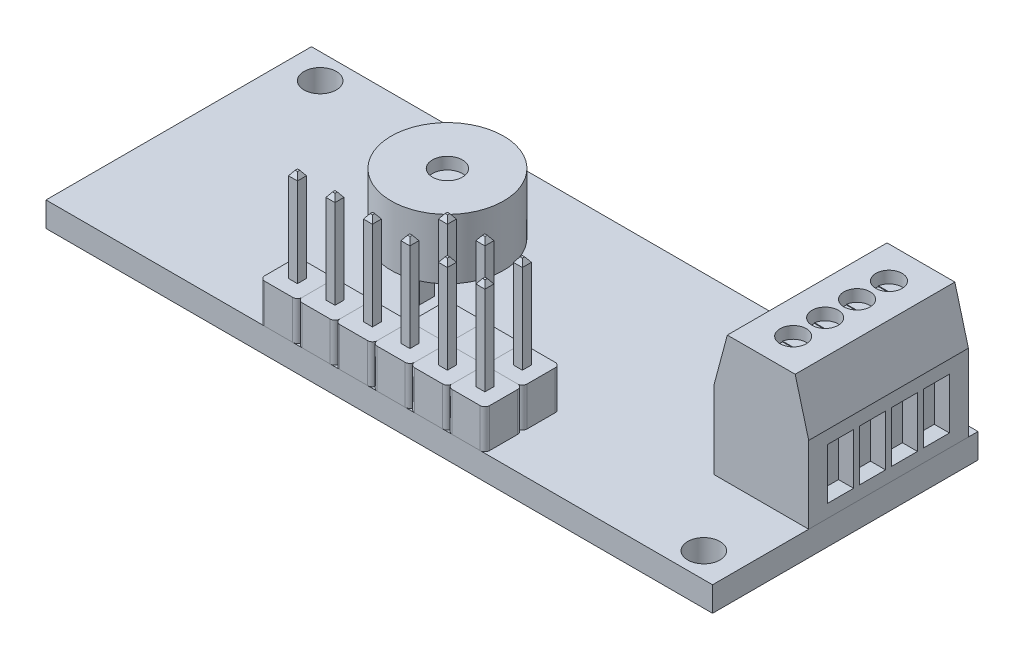
SolidWorks part; units mm, degrees
ref_plane "Front Plane" through (0, 0, 0) normal (0, 0, 1) x (1, 0, 0)
ref_plane "Top Plane" through (0, 0, 0) normal (0, 1, 0) x (1, 0, 0)
ref_plane "Right Plane" through (0, 0, 0) normal (1, 0, 0) x (0, 0, -1)
ref_axis "Axis1" through (-88.99, 0, 0) along (1, 0, 0)
ref_axis "Axis2" through (0, 55, 0) along (0, -1, 0)
ref_axis "Axis3" through (0, 0, 55) along (0, 0, -1)
ref_point "Point1"
sketch "Sketch1" plane through (0, 0, 0) normal (0, 1, 0) x (1, 0, 0)
  line L1 (-22.225, -8.8519) -> (22.225, -8.8519)
  line L2 (-22.225, -8.8519) -> (-22.225, 8.8519)
  line L3 (-22.225, 8.8519) -> (22.225, 8.8519)
  line L4 (22.225, -8.8519) -> (22.225, 8.8519)
  line L5 (-22.225, -8.8519) -> (22.225, 8.8519) construction
  line L6 (-22.225, 8.8519) -> (22.225, -8.8519) construction
  point P0 (0, 0)
  dimension "D1" = 44.45
  dimension "D2" = 17.7038
extrude "Boss-Extrude1" add sketch "Sketch1" along normal mid plane 1.651
sketch "Sketch2" plane through (0, 0.8255, 0) normal (0, 1, 0) x (1, 0, 0)
  line L0 (-21.045, 7.1769) -> (-22.225, 7.1769) construction
  line L1 (-22.225, 8.8519) -> (-22.225, -8.8519) construction
  line L2 (-19.97, 8.2519) -> (-19.97, 8.8519) construction
  line L3 (22.225, 8.8519) -> (-22.225, 8.8519) construction
  line L4 (0, 8.8519) -> (0, 0) construction
  line L5 (0, 0) -> (22.225, 0) construction
  line L6 (22.225, -8.8519) -> (22.225, 8.8519) construction
  circle A0 centre (-19.97, 7.1769) radius 1.075
  circle A3 centre (19.97, -7.1769) radius 1.075
  dimension "D1" = 2.15
  dimension "D2" = 0.6
  dimension "D3" = 1.18
extrude "Cut-Extrude1" cut sketch "Sketch2" against normal through all both and the other way through all
ref_plane "Plane1" through (0, 0, -8.2119) normal (0, 0, -1) x (-1, 0, 0)
sketch "Sketch3" plane through (0, 0, -8.2119) normal (0, 0, -1) x (-1, 0, 0)
  line L0 (-22.225, 0.8255) -> (-22.225, 5.9555)
  line L1 (-22.225, 5.9555) -> (-21.322, 9.3255)
  line L2 (-21.322, 9.3255) -> (-16.798, 9.3255)
  line L3 (-15.895, 5.9555) -> (-16.798, 9.3255)
  line L4 (-15.895, 5.9555) -> (-15.895, 0.8255)
  line L5 (-22.225, 0.8255) -> (22.225, 0.8255) construction
  line L6 (-22.225, 5.9555) -> (-15.895, 5.9555) construction
  line L7 (-19.06, 9.3255) -> (-19.06, 5.9555) construction
  line L8 (-22.225, 0.8255) -> (-15.895, 0.8255)
  dimension "D1" = 8.5
  dimension "D2" = 6.33
  dimension "D3" = 75
  dimension "D5" = 3.37
extrude "Boss-Extrude2" add sketch "Sketch3" against normal blind 10.65 separate body
sketch "Sketch4" plane through (0, 0.8255, 0) normal (0, 1, 0) x (1, 0, 0)
  line L0 (7.045, -8.8519) -> (7.045, -6.3519)
  line L1 (-22.225, -8.8519) -> (22.225, -8.8519) construction
  line L2 (7.045, -6.3519) -> (4.545, -6.3519)
  line L5 (22.225, -8.8519) -> (22.225, 8.8519) construction
  line L6 (-0.455, -7.6019) -> (2.045, -7.6019) construction
  line L7 (2.045, -7.6019) -> (4.545, -7.6019) construction
  line L8 (4.545, -7.6019) -> (7.045, -7.6019) construction
  line L10 (4.545, -8.8519) -> (4.545, -6.3519)
  line L12 (4.545, -8.8519) -> (7.045, -8.8519)
  point P15 (2.045, -7.6019)
  point P18 (4.545, -7.6019)
  dimension "D1" = 15.18
  dimension "D2" = 2.5
  dimension "D3" = 2.5
extrude "Boss-Extrude3" add sketch "Sketch4" along normal blind 2.599 separate body
sketch "Sketch5" plane through (0, 3.4245, 0) normal (0, 1, 0) x (1, 0, 0)
  line L0 (7.045, -6.3519) -> (4.545, -8.8519) construction
  line L2 (5.495, -7.3019) -> (6.095, -7.3019)
  line L3 (5.495, -7.3019) -> (5.495, -7.9019)
  line L4 (5.495, -7.9019) -> (6.095, -7.9019)
  line L5 (6.095, -7.3019) -> (6.095, -7.9019)
  line L6 (5.495, -7.3019) -> (6.095, -7.9019) construction
  line L7 (5.495, -7.9019) -> (6.095, -7.3019) construction
  point P4 (5.795, -7.6019)
  dimension "D1" = 0.6
  dimension "D2" = 0.6
extrude "Boss-Extrude4" add sketch "Sketch5" along normal blind 6.25 separate body
chamfer "Chamfer1" distance 0.3175 angle 35 4 edges at (5.495, 9.6745, 7.6019) (5.795, 9.6745, 7.3019) (6.095, 9.6745, 7.6019) (5.795, 9.6745, 7.9019) first distance on face at (5.495, 6.5495, 7.6019) first distance on face at (5.795, 6.5495, 7.3019) first distance on face at (6.095, 6.5495, 7.6019) first distance on face at (5.795, 6.5495, 7.9019)
fillet "Fillet1" radius 0.3175 4 edges at (7.045, 2.125, 6.3519) (4.545, 2.125, 6.3519) (7.045, 2.125, 8.8519) (4.545, 2.125, 8.8519)
pattern_linear "LPattern2" count 6 spacing 2.5 along (-1, 0, 0) of bodies 105 104
pattern_linear "LPattern3" count 2 spacing 2.5 along (0, 0, -1) of bodies 105 106 107 112 111 104
sketch "Sketch7" plane through (0, 0.8255, 0) normal (0, 1, 0) x (1, 0, 0)
  line L0 (-7.955, -7.6019) -> (-7.955, 8.8519) construction
  line L1 (-7.955, -6.6694) -> (-7.955, -8.5344) construction
  line L2 (22.225, 8.8519) -> (-22.225, 8.8519) construction
  line L3 (-0.455, -7.6019) -> (-0.455, 8.8519) construction
  line L4 (-0.455, -8.5344) -> (-0.455, -6.6694) construction
  line L5 (0.795, -3.8519) -> (-7.955, -3.8519) construction
  line L6 (1.7275, -3.8519) -> (-0.1375, -3.8519) construction
  circle A0 centre (-4.205, -0.1019) radius 3.75
extrude "Boss-Extrude5" add sketch "Sketch7" along normal blind 6.45 separate body
sketch "Sketch8" plane through (0, 0.8255, 0) normal (0, 1, 0) x (1, 0, 0)
  line L0 (-4.205, -0.1019) -> (-3.079, -0.1019) construction
  line L1 (-4.705, 2.2731) -> (-3.705, 2.2731)
  line L2 (-4.705, 2.2731) -> (-4.705, 1.2731)
  line L3 (-4.705, 1.2731) -> (-3.705, 1.2731)
  line L4 (-3.705, 2.2731) -> (-3.705, 1.2731)
  line L5 (-4.705, 2.2731) -> (-3.705, 1.2731) construction
  line L6 (-4.705, 1.2731) -> (-3.705, 2.2731) construction
  line L7 (-4.205, 1.7731) -> (-4.205, -0.1019) construction
  line L8 (-4.205, 1.7731) -> (-4.205, 3.6481) construction
  line L9 (-4.705, -2.4769) -> (-3.705, -2.4769)
  line L10 (-4.705, -2.4769) -> (-4.705, -1.4769)
  line L11 (-4.705, -1.4769) -> (-3.705, -1.4769)
  line L12 (-3.705, -2.4769) -> (-3.705, -1.4769)
  circle A0 centre (-4.205, -0.1019) radius 3.75 construction
  circle A1 centre (-4.205, -0.1019) radius 3.75
  point P3 (-4.205, 1.7731)
  dimension "D1" = 1
  dimension "D2" = 1
extrude "Cut-Extrude2" cut sketch "Sketch8" along normal blind 2.44
sketch "Sketch9" plane through (0, 7.2755, 0) normal (0, 1, 0) x (1, 0, 0)
  circle A0 centre (-4.205, -0.1019) radius 1
  dimension "D1" = 2
extrude "Cut-Extrude3" cut sketch "Sketch9" against normal blind 0.7937
sketch "Sketch10" plane through (0, 9.3255, 0) normal (0, 1, 0) x (1, 0, 0)
  line L0 (19.06, 8.2119) -> (19.06, 6.0819) construction
  line L1 (16.798, 8.2119) -> (21.322, 8.2119) construction
  line L2 (19.06, 6.0819) -> (19.06, 3.9519) construction
  line L3 (19.06, 3.9519) -> (19.06, 1.8219) construction
  line L4 (19.06, 1.8219) -> (19.06, -0.3081) construction
  line L5 (19.06, -0.3081) -> (19.06, -2.4381) construction
  line L6 (16.798, -2.4381) -> (21.322, -2.4381) construction
  circle A0 centre (19.06, 6.0819) radius 0.875
  circle A1 centre (19.06, 3.9519) radius 0.875
  circle A2 centre (19.06, 1.8219) radius 0.875
  circle A3 centre (19.06, -0.3081) radius 0.875
  dimension "D1" = 1.75
extrude "Cut-Extrude4" cut sketch "Sketch10" against normal blind 0.7937
sketch "Sketch11" plane through (22.225, 0, 0) normal (1, 0, 0) x (0, 0, -1)
  line L0 (-2.4381, 3.3905) -> (-0.3081, 3.3905) construction
  line L1 (-2.4381, 5.9555) -> (-2.4381, 0.8255) construction
  line L2 (-0.3081, 3.3905) -> (1.8219, 3.3905) construction
  line L3 (1.8219, 3.3905) -> (3.9519, 3.3905) construction
  line L4 (3.9519, 3.3905) -> (6.0819, 3.3905) construction
  line L5 (6.0819, 3.3905) -> (8.2119, 3.3905) construction
  line L6 (8.2119, 5.9555) -> (8.2119, 0.8255) construction
  line L8 (0.5569, 5.0905) -> (-1.1731, 5.0905)
  line L9 (0.5569, 5.0905) -> (0.5569, 1.6905)
  line L10 (0.5569, 1.6905) -> (-1.1731, 1.6905)
  line L11 (-1.1731, 5.0905) -> (-1.1731, 1.6905)
  line L12 (0.5569, 5.0905) -> (-1.1731, 1.6905) construction
  line L13 (0.5569, 1.6905) -> (-1.1731, 5.0905) construction
  dimension "D1" = 3.4
  dimension "D2" = 1.73
extrude "Cut-Extrude5" cut sketch "Sketch11" against normal blind 0.7937 draft 15
pattern_linear "LPattern4" count 4 spacing 2.13 along (0, 0, -1) of "Cut-Extrude5"
sketch "Sketch12" plane through (0, 8.5318, 0) normal (0, 1, 0) x (1, 0, 0)
  line L0 (19.935, -0.3081) -> (18.185, -0.3081) construction
  line L2 (18.1995, -0.4668) -> (19.9205, -0.4668)
  line L4 (18.1995, -0.1493) -> (19.9205, -0.1493)
  line L6 (18.185, -0.4668) -> (19.935, -0.1493) construction
  line L7 (18.185, -0.1493) -> (19.935, -0.4668) construction
  circle A0 centre (19.06, -0.3081) radius 0.875 construction
  circle A1 centre (19.06, -0.3081) radius 0.875 construction
  arc A2 (19.9205, -0.4668) -> (19.9205, -0.1493) centre (19.06, -0.3081) ccw
  circle A3 centre (19.06, -0.3081) radius 0.875
  arc A4 (18.1995, -0.1493) -> (18.1995, -0.4668) centre (19.06, -0.3081) ccw
  point P7 (19.06, -0.3081)
  dimension "D1" = 0
  dimension "D2" = 0.3175
extrude "Cut-Extrude6" cut sketch "Sketch12" against normal blind 0.0496
pattern_linear "LPattern5" count 4 spacing 2.13 along (0, 0, -1) of "Cut-Extrude6"
